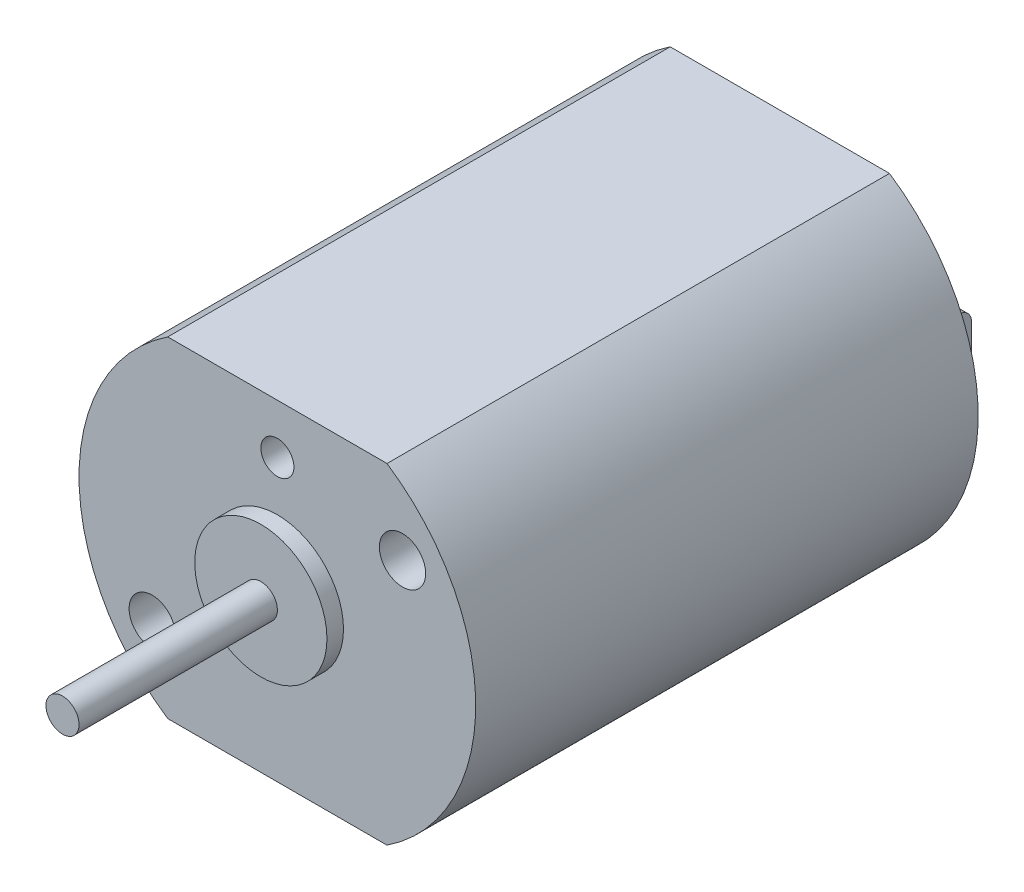
SolidWorks part; units mm, degrees
ref_plane "前视基准面" through (0, 0, 0) normal (0, 0, 1) x (1, 0, 0)
ref_plane "上视基准面" through (0, 0, 0) normal (0, 1, 0) x (1, 0, 0)
ref_plane "右视基准面" through (0, 0, 0) normal (1, 0, 0) x (0, 0, -1)
other "Configuration Table"
sketch "草图1" plane through (0, 0, 0) normal (0, 0, 1) x (1, 0, 0)
  line L0 (3.5, -0.75) -> (3.8, -0.75)
  line L1 (-6, -5) -> (6, -5)
  line L2 (-6, -5) -> (-6, 5)
  line L3 (-6, 5) -> (6, 5)
  line L4 (6, -5) -> (6, 5)
  line L5 (-6, -5) -> (6, 5) construction
  line L6 (-6, 5) -> (6, -5) construction
  line L7 (-3.8, -0.75) -> (-3.5, -0.75)
  line L8 (-3.8, -0.75) -> (-3.8, 0.75)
  line L9 (-3.8, 0.75) -> (-3.5, 0.75)
  line L10 (-3.5, -0.75) -> (-3.5, 0.75)
  line L11 (-3.8, -0.75) -> (-3.5, 0.75) construction
  line L12 (-3.8, 0.75) -> (-3.5, -0.75) construction
  line L13 (3.5, -0.75) -> (3.5, 0.75)
  line L14 (3.5, 0.75) -> (3.8, 0.75)
  line L15 (3.8, -0.75) -> (3.8, 0.75)
  line L16 (-3.5, 0) -> (3.5, 0) construction
  circle A0 centre (0, 0) radius 6
  circle A1 centre (0, 0) radius 2.5
  circle A2 centre (0, 0) radius 1.5
  point P0 (0, 0)
  point P8 (-3.65, 0)
  dimension "D6" = 5
  dimension "D7" = 3
  dimension "D1" = 12
  dimension "D2" = 10
  dimension "D3" = 0.3
  dimension "D4" = 1.5
  dimension "D5" = 7
extrude "凸台-拉伸1" add sketch "草图1" along normal blind 15.2 contours L3 A0 L1 A1 L15 L0 L13 L14 L10 L7 L8 L9 | A1 A2 | A2 | L0 L15 L14 L13 | L7 L10 L9 L8 region at (3.65, 0, 0) region at (-5.1491, -2.7634, 0) region at (-3.65, 0, 0) region at (-2.4293, 0, 0) region at (0, 0, 0)
extrude "凸台-拉伸2" add sketch "草图1<4>" against normal blind 2 contours L13 L14 L15 L0 | L8 L9 L10 L7
sketch "草图1<4>" plane through (0, 0, 0) normal (0, 0, 1) x (1, 0, 0) same geometry as "草图1"
sketch "草图2" plane through (3.8, 0, 0) normal (1, 0, 0) x (0, 0, -1)
  line L0 (0.95, 0) -> (1.05, 0) construction
  line L1 (0.95, 0.45) -> (1.05, 0.45)
  line L2 (0.95, -0.45) -> (1.05, -0.45)
  line L4 (1, 0.75) -> (1, -0.75) construction
  line L5 (2, 0.75) -> (0, 0.75) construction
  line L6 (2, -0.75) -> (0, -0.75) construction
  arc A0 (0.95, 0.45) -> (0.95, -0.45) centre (0.95, 0) ccw
  arc A1 (1.05, -0.45) -> (1.05, 0.45) centre (1.05, 0) ccw
  point P3 (1, 0)
  dimension "D2" = 0.45
  dimension "D1" = 0.1
extrude "切除-拉伸2" cut sketch "草图2" against normal through all
fillet "圆角1" radius 0.4 4 edges at (-3.65, 0.75, -2) (-3.65, -0.75, -2) (3.65, 0.75, -2) (3.65, -0.75, -2)
extrude "凸台-拉伸3" add sketch "草图1<5>" against normal blind 1.2 contours A1 A2 | A2 region at (-2.4293, 0, 0) region at (0, 0, 0)
sketch "草图1<5>" plane through (0, 0, 0) normal (0, 0, 1) x (1, 0, 0) same geometry as "草图1"
extrude "切除-拉伸1" cut sketch "草图1<7>" along normal blind 0.6 from surface contours A2 region at (0, 0, 0) starting at face at (2.5, 0, -1.2)
sketch "草图1<7>" plane through (0, 0, 0) normal (0, 0, 1) x (1, 0, 0) same geometry as "草图1"
fillet "圆角2" radius 0.4 1 edges at (2.5, 0, -1.2)
sketch "草图3" plane through (0, 0, 15.2) normal (0, 0, 1) x (1, 0, 0)
  circle A0 centre (0, 0) radius 2
  circle A1 centre (0, 0) radius 0.5
  dimension "D1" = 4
  dimension "D2" = 1
extrude "凸台-拉伸4" add sketch "草图3" along normal blind 0.5 contours A0
extrude "凸台-拉伸5" add sketch "草图3<3>" along normal blind 6.5 contours A1 region at (0, 0, 15.2)
sketch "草图3<3>" plane through (0, 0, 15.2) normal (0, 0, 1) x (1, 0, 0) same geometry as "草图3"
sketch "草图4" plane through (0, 0, 15.2) normal (0, 0, 1) x (1, 0, 0)
  line L0 (-3.7858, -2.7) -> (3.7858, 2.7) construction
  line L1 (0, 0) -> (0, 5) construction
  line L2 (-3.3166, 5) -> (3.3166, 5) construction
  circle A0 centre (-3.7858, -2.7) radius 0.7
  circle A1 centre (3.7858, 2.7) radius 0.7
  circle A2 centre (0, 3.5) radius 0.5
  dimension "D1" = 1.4
  dimension "D2" = 9.3
  dimension "D3" = 1
  dimension "D4" = 3.5
  dimension "D5" = 5.4
extrude "切除-拉伸3" cut sketch "草图4" against normal blind 1
